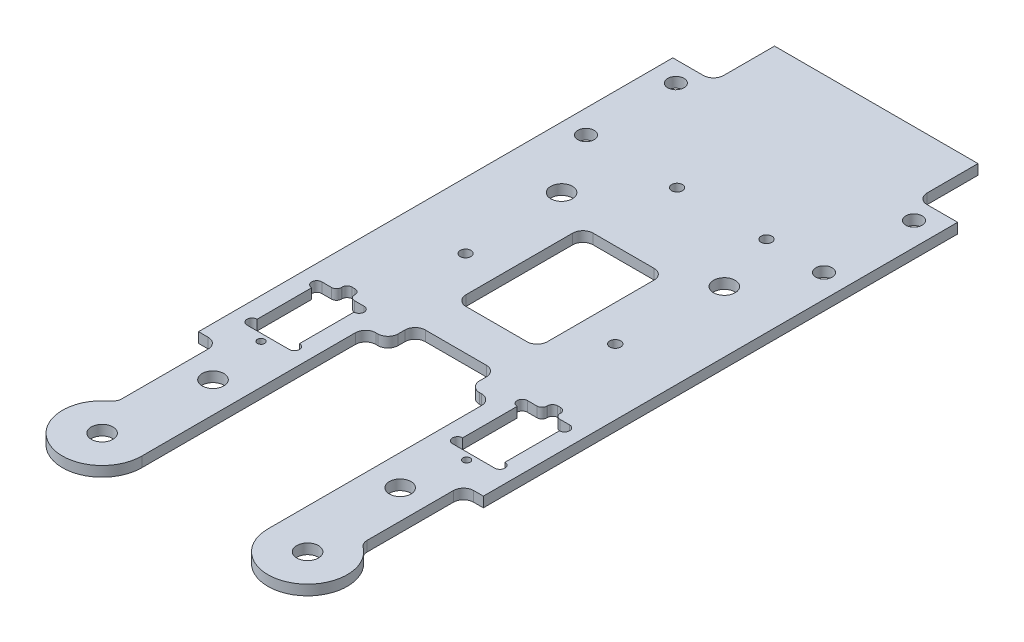
SolidWorks part; units mm, degrees
material "6061-T4 (SS)"
ref_plane "Front Plane" through (0, 0, 0) normal (0, 0, 1) x (1, 0, 0)
ref_plane "Top Plane" through (0, 0, 0) normal (0, 1, 0) x (1, 0, 0)
ref_plane "Right Plane" through (0, 0, 0) normal (1, 0, 0) x (0, 0, -1)
sketch "Sketch1" plane through (0, 0, 0) normal (0, 1, 0) x (1, 0, 0)
  line L1 (-44.45, -114.3) -> (44.45, -114.3)
  line L2 (-44.45, -114.3) -> (-44.45, 114.3)
  line L3 (-44.45, 114.3) -> (44.45, 114.3)
  line L4 (44.45, -114.3) -> (44.45, 114.3)
  line L5 (-44.45, -114.3) -> (44.45, 114.3) construction
  line L6 (-44.45, 114.3) -> (44.45, -114.3) construction
  point P0 (0, 0)
  dimension "D1" = 88.9
  dimension "D2" = 228.6
extrude "Boss-Extrude1" add sketch "Sketch1" along normal blind 3.175
sketch "Sketch11" plane through (0, 3.175, 0) normal (0, 1, 0) x (1, 0, 0)
  line L0 (0, 31.75) -> (97.4414, 31.75) construction
  line L10 (0, 0) -> (0, 114.3) construction
  line L14 (44.45, 114.3) -> (-44.45, 114.3) construction
  line L15 (0, 0) -> (117.475, 0) construction
  circle A0 centre (-26.289, 4.9828) radius 1.25
  circle A1 centre (-25.019, 53.1832) radius 1.25
  circle A2 centre (25.781, 38.1972) radius 1.25
  circle A3 centre (25.781, 10.0628) radius 1.25
  dimension "D3" = 2.5
  dimension "D5" = 2.5
  dimension "D7" = 31.75
  dimension "D9" = 25.781
  dimension "D4" = 2.5
  dimension "D6" = 2.5
  dimension "D2" = 25.019
  dimension "D8" = 26.289
  dimension "D10" = 6.4472
  dimension "D11" = 25.781
  dimension "D12" = 21.6872
  dimension "D13" = 26.7672
  dimension "D14" = 21.4332
extrude "Cut-Extrude12" [suppressed] cut sketch "Sketch11" against normal through all
sketch "Sketch18" plane through (0, 3.175, 0) normal (0, 1, 0) x (1, 0, 0)
  line L0 (44.45, 79.883) -> (-44.45, 79.883) construction
  line L1 (44.45, -114.3) -> (44.45, 114.3) construction
  line L2 (-44.45, 114.3) -> (-44.45, -114.3) construction
  line L3 (44.45, 114.3) -> (-44.45, 114.3) construction
  line L4 (0, 79.883) -> (0, -114.3) construction
  line L5 (-44.45, -114.3) -> (44.45, -114.3) construction
  circle A9 centre (-23.9014, 29.083) radius 1.6891
  circle A10 centre (23.9014, 27.9832) radius 1.6891
  circle A11 centre (-8.702, 79.883) radius 1.6891
  circle A12 centre (19.1999, 79.883) radius 1.6891
  dimension "D4" = 50.8
  dimension "D9" = 15.1994
  dimension "D11" = 3.3782
  dimension "D13" = 43.1013
  dimension "D3" = 3.3782
  dimension "D2" = 3.3782
  dimension "D8" = 3.3782
  dimension "D1" = 34.417
  dimension "D5" = 23.9014
  dimension "D6" = 47.8028
  dimension "D7" = 1.0998
  dimension "D10" = 50.8
  dimension "D12" = 50.8
sketch "Sketch12" plane through (0, 3.175, 0) normal (0, 1, 0) x (1, 0, 0)
  line L0 (0, 0) -> (44.45, 0) construction
  line L1 (44.45, -114.3) -> (44.45, 114.3) construction
  line L2 (0, 0) -> (0, 114.3) construction
  line L3 (44.45, 114.3) -> (-44.45, 114.3) construction
  line L4 (44.45, -44.45) -> (-44.45, -44.45) construction
  line L5 (-19.685, -69.85) -> (19.685, -69.85)
  line L6 (-19.685, -69.85) -> (-19.685, -6.35)
  line L7 (-19.685, -6.35) -> (19.685, -6.35)
  line L8 (19.685, -69.85) -> (19.685, -6.35)
  line L9 (-19.685, -69.85) -> (19.685, -6.35) construction
  line L10 (-19.685, -6.35) -> (19.685, -69.85) construction
  line L11 (-44.45, 114.3) -> (-44.45, -114.3) construction
  line L12 (0, -38.1) -> (0, -114.3) construction
  line L13 (-44.45, -114.3) -> (44.45, -114.3) construction
  circle A0 centre (29.21, -44.45) radius 3.3782
  circle A1 centre (-29.21, -44.45) radius 3.3782
  point P5 (0, -38.1)
  dimension "D5" = 6.7564
  dimension "D1" = 63.5
  dimension "D2" = 38.1
  dimension "D3" = 39.37
  dimension "D4" = 25.4
  dimension "D6" = 58.42
extrude "Cut-Extrude13" cut sketch "Sketch12" against normal through all
sketch "Sketch14" plane through (0, 0, 0) normal (0, -1, 0) x (-1, 0, 0)
  line L0 (0, 114.3) -> (0, 31.056) construction
  line L1 (-44.45, 114.3) -> (44.45, 114.3) construction
  line L2 (0, 114.3) -> (-44.45, 114.3) construction
  line L3 (-41.91, 114.3) -> (-41.91, 67.4804) construction
  line L5 (-32.385, 114.3) -> (-32.385, 67.4804) construction
  line L6 (-32.385, 107.95) -> (-41.91, 107.95) construction
  line L7 (-32.385, 93.9165) -> (-41.91, 93.9165) construction
  line L8 (-44.45, -114.3) -> (-44.45, 114.3) construction
  circle A0 centre (-37.1475, 107.95) radius 2.5527
  circle A1 centre (-37.1475, 79.883) radius 2.5527
  circle A2 centre (37.1475, 107.95) radius 2.5527
  circle A3 centre (37.1475, 79.883) radius 2.5527
  dimension "D4" = 5.1054
  dimension "D1" = 2.54
  dimension "D2" = 9.525
  dimension "D3" = 6.35
  dimension "D5" = 14.0335
extrude "Cut-Extrude15" cut sketch "Sketch14" against normal through all
sketch "Sketch15" plane through (0, 0, 0) normal (0, -1, 0) x (1, 0, 0)
  line L0 (44.45, 114.3) -> (44.45, -114.3) construction
  line L1 (-44.45, 114.3) -> (44.45, 114.3)
  line L2 (-44.45, 114.3) -> (-44.45, 57.15)
  line L3 (-44.45, 57.15) -> (44.45, 57.15)
  line L4 (44.45, 114.3) -> (44.45, 57.15)
  line L5 (19.685, 6.35) -> (-19.685, 6.35) construction
  line L6 (0, -24.0665) -> (0, -114.3) construction
  line L7 (12.7, -51.308) -> (12.7, -17.9917)
  line L8 (9.525, -14.8167) -> (-9.525, -14.8167)
  line L9 (44.45, -114.3) -> (-44.45, -114.3) construction
  line L10 (-12.7, -17.9917) -> (-12.7, -51.308)
  line L11 (9.525, -54.483) -> (-9.525, -54.483)
  line L12 (12.7, -51.308) -> (12.7, 6.35) construction
  line L13 (12.7, 6.35) -> (-12.7, 6.35) construction
  line L14 (-12.7, -51.308) -> (-12.7, 6.35) construction
  line L15 (12.7, -54.483) -> (-12.7, 6.35) construction
  line L16 (12.7, 6.35) -> (-12.7, -54.483) construction
  line L17 (12.7, 6.35) -> (-12.7, 6.35)
  line L18 (-12.7, 6.35) -> (-12.7, 1.0583)
  line L19 (-9.525, -2.1167) -> (9.525, -2.1167)
  line L20 (12.7, 1.0583) -> (12.7, 6.35)
  circle A0 centre (-29.21, 44.45) radius 3.3782 construction
  circle A1 centre (-37.1475, -79.883) radius 2.5527 construction
  arc A2 (-9.525, -54.483) -> (-12.7, -51.308) centre (-9.525, -51.308) cw
  arc A3 (9.525, -54.483) -> (12.7, -51.308) centre (9.525, -51.308) ccw
  arc A4 (12.7, -17.9917) -> (9.525, -14.8167) centre (9.525, -17.9917) ccw
  arc A5 (-9.525, -14.8167) -> (-12.7, -17.9917) centre (-9.525, -17.9917) ccw
  arc A6 (-12.7, 1.0583) -> (-9.525, -2.1167) centre (-9.525, 1.0583) ccw
  arc A7 (9.525, -2.1167) -> (12.7, 1.0583) centre (9.525, 1.0583) ccw
  point P35 (12.7, -14.8167)
  point P38 (-12.7, -14.8167)
  point P41 (-12.7, -2.1167)
  point P44 (12.7, -2.1167)
  dimension "D3" = 3.175
  dimension "D7" = 3.175
  dimension "D1" = 12.7
  dimension "D2" = 25.4
  dimension "D4" = 25.4
  dimension "D5" = 8.4667
  dimension "D6" = 12.7
extrude "Cut-Extrude16" cut sketch "Sketch15" against normal through all
fillet "Fillet1" radius 3.175 4 edges at (19.685, 1.5875, 6.35) (-19.685, 1.5875, 6.35) (-12.7, 1.5875, 6.35) (12.7, 1.5875, 6.35)
extrude "Cut-Extrude18" cut sketch "Sketch18" against normal through all
sketch "Sketch16" plane through (0, 3.175, 0) normal (0, 1, 0) x (1, 0, 0)
  line L0 (44.45, -57.15) -> (44.45, -76.2)
  line L1 (19.685, -57.15) -> (19.685, -76.2)
  line L2 (19.685, -76.2) -> (44.45, -76.2) construction
  line L3 (0, 0) -> (0, -94.827) construction
  line L4 (44.45, -57.15) -> (19.685, -57.15)
  line L5 (-19.685, -57.15) -> (-19.685, -76.2)
  line L6 (-44.45, -57.15) -> (-19.685, -57.15)
  line L7 (-44.45, -57.15) -> (-44.45, -76.2)
  arc A0 (44.45, -76.2) -> (19.685, -76.2) centre (32.0675, -76.2) cw
  arc A1 (-44.45, -76.2) -> (-19.685, -76.2) centre (-32.0675, -76.2) ccw
  circle A2 centre (32.0675, -76.2) radius 3.3782
  circle A3 centre (-32.0675, -76.2) radius 3.3782
  line M12 (-44.45, -57.15) -> (-19.685, -57.15)
  line M16 (19.685, -57.15) -> (44.45, -57.15)
  dimension "D2" = 6.7564
  dimension "D1" = 19.05
extrude "Boss-Extrude2" add sketch "Sketch16" against normal up to surface (3.175 mm away) contours L7 A1 L5 A3 M12 | A0 L0 L1 A2 M16 region at (32.0675, 3.175, 71.4304) region at (-32.0675, 3.175, 71.4304) up to face at (23.9014, 0, -26.2941)
sketch "Sketch19" plane through (0, 3.175, 0) normal (0, 1, 0) x (1, 0, 0)
  line L0 (0, 14.8167) -> (0, 54.483) construction
  line L1 (9.525, 14.8167) -> (-9.525, 14.8167) construction
  line L2 (-9.525, 54.483) -> (9.525, 54.483) construction
  line L4 (-12.7, 17.9917) -> (-12.7, 51.308) construction
  line L6 (-38.1, 53.975) -> (-12.7, 53.975) construction
  line L7 (-25.4, 53.975) -> (-25.4, 60.5367) construction
  line L9 (-44.45, 114.3) -> (-44.45, -76.2) construction
  circle A0 centre (-25.4, 60.5367) radius 3.3782
  circle A1 centre (25.4, 60.5367) radius 3.3782
  dimension "D1" = 6.7564
  dimension "D2" = 45.72
  dimension "D3" = 6.35
extrude "Cut-Extrude19" cut sketch "Sketch19" against normal through all
sketch "Sketch20" plane through (0, 3.175, 0) normal (0, 1, 0) x (1, 0, 0)
  line L0 (0, 0) -> (0, 61.1006) construction
  line L3 (-25.8445, 3.175) -> (-25.8445, -28.575) construction
  line L6 (-25.4635, -1.016) -> (-38.6715, -1.016) construction
  line L7 (-25.4635, -1.016) -> (-25.4635, -24.384) construction
  line L8 (-25.4635, -24.384) -> (-38.6715, -24.384)
  line L9 (-38.6715, -1.016) -> (-38.6715, -24.384) construction
  line L10 (-25.4635, -1.016) -> (-38.6715, -24.384) construction
  line L11 (-25.4635, -24.384) -> (-38.6715, -1.016) construction
  line L13 (-38.2905, 3.175) -> (-38.2905, -28.575) construction
  line L14 (-25.8445, 3.175) -> (-38.2905, -28.575) construction
  line L27 (-32.0675, -76.2) -> (-32.0675, 23.1424) construction
  line L28 (-38.2905, 3.175) -> (-25.8445, -28.575) construction
  line L29 (-38.2905, -28.575) -> (-32.9565, -28.575) construction
  line L30 (-32.9565, -28.575) -> (-32.9565, -27.305) construction
  line L31 (-31.1785, -28.575) -> (-31.1785, -27.305) construction
  line L32 (-25.8445, -28.575) -> (-31.1785, -28.575) construction
  line L33 (-25.8445, 3.175) -> (-31.1785, 3.175) construction
  line L34 (-31.1785, 3.175) -> (-31.1785, 1.905) construction
  line L35 (-32.9565, 3.175) -> (-32.9565, 1.905) construction
  line L36 (-38.2905, 3.175) -> (-32.9565, 3.175) construction
  line L38 (-30.0355, 0.5715) -> (-30.0355, 0.6985)
  line L42 (-28.448, -1.016) -> (-25.4635, -1.016)
  line L44 (-34.0995, 0.5715) -> (-34.0995, 0.6985)
  line L45 (-35.687, -1.016) -> (-38.6715, -1.016)
  line L48 (-32.0675, 1.1866) -> (-32.0675, 0.0436) construction
  line L49 (-32.0675, 1.1866) -> (-32.0675, 0.0436) construction
  line L50 (-32.512, 2.286) -> (-31.623, 2.286)
  line L85 (-25.4635, -4.191) -> (-25.4635, -21.209)
  line L86 (-38.6715, -4.191) -> (-38.6715, -21.209)
  line L87 (25.4635, -24.384) -> (38.6715, -24.384)
  line L88 (25.4635, -4.191) -> (25.4635, -21.209)
  line L89 (28.448, -1.016) -> (25.4635, -1.016)
  line L90 (30.0355, 0.5715) -> (30.0355, 0.6985)
  line L91 (32.512, 2.286) -> (31.623, 2.286)
  line L92 (34.0995, 0.5715) -> (34.0995, 0.6985)
  line L93 (35.687, -1.016) -> (38.6715, -1.016)
  line L94 (38.6715, -4.191) -> (38.6715, -21.209)
  arc A0 (-32.9565, -27.305) -> (-31.1785, -27.305) centre (-32.0675, -26.5866) cw construction
  circle A3 centre (-32.0675, -26.5866) radius 1.143
  arc A9 (-30.0355, 0.6985) -> (-31.623, 2.286) centre (-31.623, 0.6985) ccw
  arc A10 (-32.512, 2.286) -> (-34.0995, 0.6985) centre (-32.512, 0.6985) ccw
  arc A16 (-30.0355, 0.5715) -> (-28.448, -1.016) centre (-28.448, 0.5715) ccw
  arc A17 (-34.0995, 0.5715) -> (-35.687, -1.016) centre (-35.687, 0.5715) cw
  arc A23 (-25.4635, -24.384) -> (-25.4635, -21.209) centre (-25.4635, -22.7965) ccw
  arc A24 (-25.4635, -1.016) -> (-25.4635, -4.191) centre (-25.4635, -2.6035) cw
  arc A25 (-38.6715, -24.384) -> (-38.6715, -21.209) centre (-38.6715, -22.7965) cw
  arc A26 (-38.6715, -1.016) -> (-38.6715, -4.191) centre (-38.6715, -2.6035) ccw
  circle A27 centre (32.0675, -26.5866) radius 1.143
  arc A28 (25.4635, -24.384) -> (25.4635, -21.209) centre (25.4635, -22.7965) cw
  arc A29 (25.4635, -1.016) -> (25.4635, -4.191) centre (25.4635, -2.6035) ccw
  arc A30 (30.0355, 0.5715) -> (28.448, -1.016) centre (28.448, 0.5715) cw
  arc A31 (30.0355, 0.6985) -> (31.623, 2.286) centre (31.623, 0.6985) cw
  arc A32 (32.512, 2.286) -> (34.0995, 0.6985) centre (32.512, 0.6985) cw
  arc A33 (34.0995, 0.5715) -> (35.687, -1.016) centre (35.687, 0.5715) ccw
  arc A34 (38.6715, -1.016) -> (38.6715, -4.191) centre (38.6715, -2.6035) cw
  arc A35 (38.6715, -24.384) -> (38.6715, -21.209) centre (38.6715, -22.7965) ccw
  point P10 (-32.0675, -12.7)
  point P16 (-32.0675, -12.7)
  point P38 (-30.0355, 2.286)
  point P45 (-34.0995, 2.286)
  point P54 (-30.0355, -1.016)
  point P57 (-34.0995, -1.016)
  dimension "D6" = 1.5875
  dimension "D7" = 1.5875
  dimension "D8" = 1.5875
  dimension "D9" = 1.5875
  dimension "D1" = 13.208
  dimension "D2" = 23.368
  dimension "D3" = 63.5
  dimension "D4" = 2.032
  dimension "D5" = 3.302
extrude "Cut-Extrude20" cut sketch "Sketch20" against normal through all
sketch "Sketch21" plane through (0, 0, -114.3) normal (0, 0, -1) x (-1, 0, 0)
  line L1 (44.45, 0) -> (-44.45, 0)
  line L2 (44.45, 0) -> (44.45, 3.175)
  line L3 (44.45, 3.175) -> (-44.45, 3.175)
  line L4 (-44.45, 0) -> (-44.45, 3.175)
extrude "Boss-Extrude3" add sketch "Sketch21" along normal blind 19.05
sketch "Sketch22" plane through (0, 3.175, 0) normal (0, 1, 0) x (1, 0, 0)
  line L0 (0, 54.483) -> (0, 133.35) construction
  line L1 (-44.45, 133.35) -> (-31.75, 133.35)
  line L2 (-44.45, 133.35) -> (-44.45, 114.3)
  line L3 (-44.45, 114.3) -> (-34.925, 114.3)
  line L4 (-31.75, 133.35) -> (-31.75, 117.475)
  line L5 (-9.525, 54.483) -> (9.525, 54.483) construction
  line L6 (44.45, 133.35) -> (-44.45, 133.35) construction
  line L7 (44.45, 114.3) -> (34.925, 114.3)
  line L8 (31.75, 133.35) -> (31.75, 117.475)
  line L9 (44.45, 133.35) -> (31.75, 133.35)
  line L10 (44.45, 133.35) -> (44.45, 114.3)
  arc A0 (-34.925, 114.3) -> (-31.75, 117.475) centre (-34.925, 117.475) ccw
  arc A1 (34.925, 114.3) -> (31.75, 117.475) centre (34.925, 117.475) cw
  point P13 (-31.75, 114.3)
  dimension "D3" = 3.175
  dimension "D1" = 12.7
  dimension "D2" = 19.05
extrude "Cut-Extrude21" cut sketch "Sketch22" against normal through all
sketch "Sketch23" plane through (0, 3.175, 0) normal (0, 1, 0) x (1, 0, 0)
  line L0 (-38.2587, -63.7779) -> (-38.2587, -36.9014)
  line L1 (-41.4337, -33.7264) -> (-44.45, -33.7264)
  line L2 (-44.45, 114.3) -> (-44.45, -76.2) construction
  line L3 (-44.45, -33.7264) -> (-44.45, -76.2)
  line L4 (0, 0) -> (0, -80.0101) construction
  line L5 (41.4337, -33.7264) -> (44.45, -33.7264)
  line L6 (38.2587, -63.7779) -> (38.2587, -36.9014)
  line L7 (44.45, -33.7264) -> (44.45, -76.2)
  circle A0 centre (-32.0675, -76.2) radius 12.3825 construction
  arc A1 (-44.45, -76.2) -> (-39.5223, -66.313) centre (-32.0675, -76.2) cw
  arc A2 (-39.5223, -66.313) -> (-38.2587, -63.7779) centre (-41.4337, -63.7779) ccw
  arc A3 (-38.2587, -36.9014) -> (-41.4337, -33.7264) centre (-41.4337, -36.9014) ccw
  arc A4 (38.2587, -36.9014) -> (41.4337, -33.7264) centre (41.4337, -36.9014) cw
  arc A5 (39.5223, -66.313) -> (38.2587, -63.7779) centre (41.4337, -63.7779) cw
  arc A6 (44.45, -76.2) -> (39.5223, -66.313) centre (32.0675, -76.2) ccw
  point P12 (-38.2587, -65.4764)
  point P15 (-38.2587, -33.7264)
  dimension "D1" = 60
  dimension "D3" = 3.175
  dimension "D2" = 31.75
extrude "Cut-Extrude22" cut sketch "Sketch23" against normal through all
